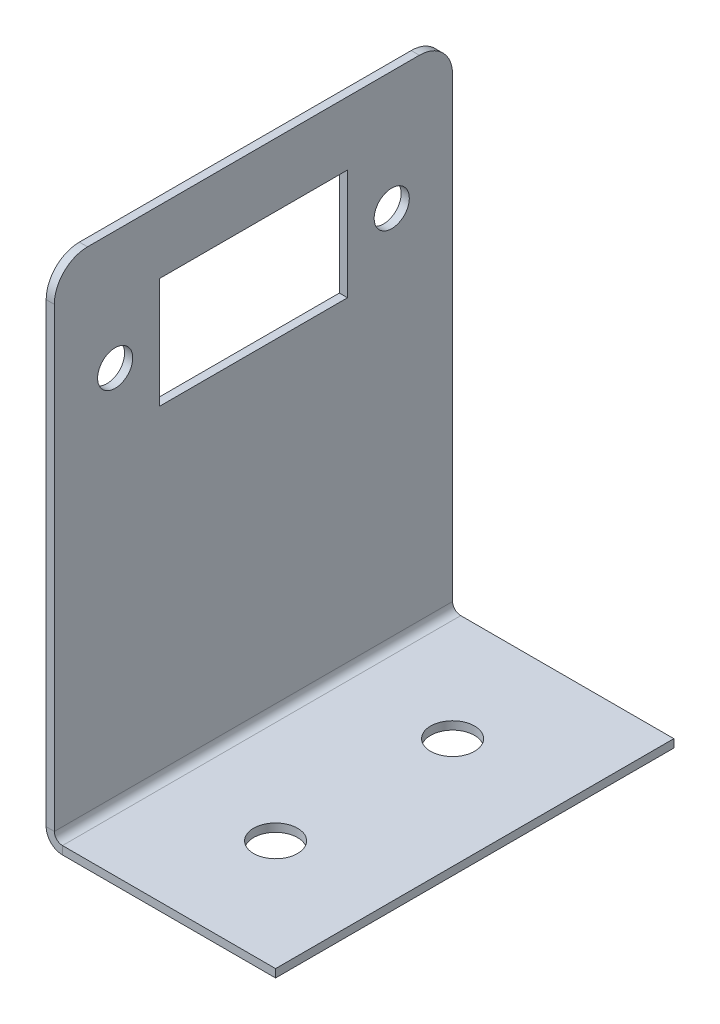
SolidWorks part; units mm, degrees
note: The reader was unsure of these and kept them because the rebuilt part matched: bend radius of "BaseBend1".
material "Plain Carbon Steel"
ref_plane "Front Plane" through (0, 0, 0) normal (0, 0, 1) x (1, 0, 0)
ref_plane "Top Plane" through (0, 0, 0) normal (0, 1, 0) x (1, 0, 0)
ref_plane "Right Plane" through (0, 0, 0) normal (1, 0, 0) x (0, 0, -1)
sketch "Sketch1" plane through (0, 0, 0) normal (0, 0, 1) x (1, 0, 0)
  line L0 (0, 45) -> (0, 0)
  line L1 (0, 0) -> (20, 0)
  dimension "D1" = 20
  dimension "D2" = 45
base flange "Base-Flange1" sketch "Sketch1" end condition mid plane depth 36 reverse direction no thickness 0.7366 reverse thickness direction no bend radius 0.7366
bend "BaseBend1" bend radius 0.7366 bend angle 90 parameters "D5"=1
sketch "Sketch6" plane through (0, 0, 0) normal (1, 0, 0) x (0, 0, -1)
  line L0 (0, 10.5504) -> (0, 51.8416) construction
  line L1 (-8.5, 39.2634) -> (8.5, 39.2634)
  line L2 (-8.5, 39.2634) -> (-8.5, 29.2634)
  line L3 (-8.5, 29.2634) -> (8.5, 29.2634)
  line L4 (8.5, 39.2634) -> (8.5, 29.2634)
  line L5 (21.465, 34.2634) -> (-23.8382, 34.2634) construction
  line L6 (-18, -0.7366) -> (18, -0.7366) construction
  circle A0 centre (-12.5, 34.2634) radius 1.5875
  circle A1 centre (12.5, 34.2634) radius 1.5875
  dimension "D4" = 3.175
  dimension "D5" = 25
  dimension "D1" = 17
  dimension "D2" = 10
  dimension "D3" = 30
extrude "Cut-Extrude1" cut sketch "Sketch6" against normal through all normal cut yes
sketch "Sketch7" plane through (0, 0, 0) normal (0, 1, 0) x (1, 0, 0)
  line L0 (3.8032, 0) -> (28.656, 0) construction
  line L1 (20, -18) -> (20, 18) construction
  circle A0 centre (10, 8) radius 1.9844
  circle A1 centre (10, -8) radius 1.9844
  dimension "D1" = 3.9688
  dimension "D2" = 10
  dimension "D3" = 16
extrude "Cut-Extrude2" cut sketch "Sketch7" against normal through all normal cut yes
fillet "Fillet1" radius 3 2 edges at (-0.3683, 45, -18) (-0.3683, 45, 18)
sketch "Bend-Lines1" [suppressed] plane through (0, 0, 0) normal (0, 1, 0) x (1, 0, 0)
sketch "Bounding-Box1" [suppressed] plane through (0, 0, 0) normal (0, 1, 0) x (1, 0, 0)
sheet metal parameters "Sheet-Metal3" thickness 0.7366 parameters "D1"=0.7366
flat pattern "Flat-Pattern3" [suppressed]
sketch "Bend-Lines2" plane through (0, 0, 0) normal (0, 1, 0) x (1, 0, 0)
sketch "Bounding-Box2" [suppressed] plane through (0, 0, 0) normal (0, 1, 0) x (1, 0, 0)
bend of the flat pattern "Flatten-<BaseBend1>1"
sheet metal parameters "Sheet-Metal4" thickness 0.7366 parameters "D1"=0.7366
flat pattern "Flat-Pattern3" [suppressed]
sketch "Bend-Lines2" plane through (0, 0, 0) normal (0, 1, 0) x (1, 0, 0)
sketch "Bounding-Box2" [suppressed] plane through (0, 0, 0) normal (0, 1, 0) x (1, 0, 0)
bend of the flat pattern "Flatten-<BaseBend1>1"
sheet metal parameters "Sheet-Metal5" thickness 0.7366 parameters "D1"=0.7366
flat pattern "Flat-Pattern3"
sketch "Bend-Lines2" plane through (0, 0, 0) normal (1, 0, 0) x (0, 0, -1)
  line L0 (18, -0.1312) -> (-18, -0.1312) construction
  line L1 (18, -0.1312) -> (-18, -0.1312) construction
sketch3d "Bounding-Box2" [suppressed]
  line L0 (0, -65.2624, 0) -> (0, 0, 0) construction
  line L1 (36, -65.2624, 0) -> (36, 0, 0) construction
  line L2 (0, -65.2624, 0) -> (36, -65.2624, 0) construction
  line L3 (0, 0, 0) -> (36, 0, 0) construction
bend of the flat pattern "Flatten-<BaseBend1>1"
